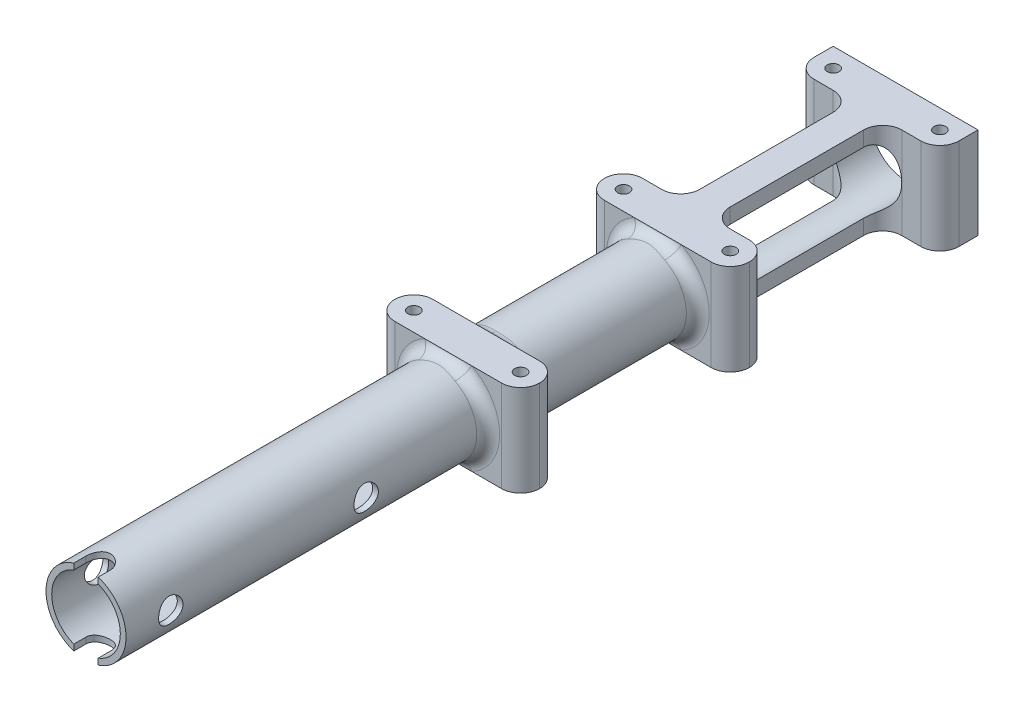
SolidWorks part; units mm, degrees
material "6063-T6"
ref_plane "Front Plane" through (0, 0, 0) normal (0, 0, 1) x (1, 0, 0)
ref_plane "Top Plane" through (0, 0, 0) normal (0, 1, 0) x (1, 0, 0)
ref_plane "Right Plane" through (0, 0, 0) normal (1, 0, 0) x (0, 0, -1)
sketch "Sketch1" plane through (0, 0, 0) normal (0, 0, 1) x (1, 0, 0)
  circle A1 centre (0, 0) radius 10.5
  dimension "D1" = 21
extrude "Boss-Extrude1" add sketch "Sketch1" along normal blind 150
sketch "Sketch3" plane through (0, 0, 0) normal (0, 1, 0) x (1, 0, 0)
  line L0 (0, 0) -> (0, 101.6874) construction
  line L2 (19, 0) -> (-19, 0)
  line L3 (-19, 0) -> (-19, 10)
  line L4 (-19, 10) -> (-4, 10)
  line L5 (-4, 10) -> (-4, 55)
  line L6 (-4, 55) -> (-19, 55)
  line L7 (-19, 55) -> (-19, 65)
  line L8 (-19, 65) -> (19, 65)
  line L9 (19, 55) -> (19, 65)
  line L10 (4, 55) -> (19, 55)
  line L11 (4, 10) -> (4, 55)
  line L12 (19, 10) -> (4, 10)
  line L13 (19, 0) -> (19, 10)
  line L14 (-19, 5) -> (35.7917, 5) construction
  line L15 (-19, 60) -> (20.8388, 60) construction
  line L16 (14, -50) -> (-14, -50) construction
  line L24 (0, -50) -> (0, 0) construction
  line L28 (-19, -55) -> (19, -55)
  line L29 (-19, -55) -> (-19, -45)
  line L30 (-19, -45) -> (19, -45)
  line L31 (19, -55) -> (19, -45)
  line L32 (-19, -55) -> (19, -45) construction
  line L33 (-19, -45) -> (19, -55) construction
  circle A0 centre (-14, 5) radius 1.55
  circle A1 centre (14, 5) radius 1.55
  circle A4 centre (-14, 60) radius 1.55
  circle A5 centre (14, 60) radius 1.55
  circle A6 centre (14, -50) radius 1.55
  circle A7 centre (-14, -50) radius 1.55
  point P12 (0, 65)
  dimension "D6" = 3.1
  dimension "D8" = 3.1
  dimension "D11" = 28
  dimension "D12" = 55
  dimension "D13" = 28
  dimension "D7" = 28
  dimension "D2" = 45
  dimension "D3" = 10
  dimension "D4" = 10
  dimension "D5" = 8
  dimension "D10" = 38
  dimension "D14" = 38
  dimension "D16" = 10
  dimension "D17" = 38
extrude "Boss-Extrude2" add sketch "Sketch3" along normal blind 12 and the other way blind 12
sketch "Sketch6" plane through (0, 0, 0) normal (0, 0, 1) x (1, 0, 0)
  circle A0 centre (0, 0) radius 9
  dimension "D1" = 18
extrude "Cut-Extrude1" cut sketch "Sketch6" against normal through all both and the other way through all
sketch "Sketch7" plane through (0, 0, 0) normal (1, 0, 0) x (0, 0, -1)
  line L0 (-150, 9) -> (-150, -9) construction
  line L1 (-138.25, 0) -> (0, 0) construction
  circle A0 centre (-87, 0) radius 3.2
  circle A1 centre (-138.25, 0) radius 3.2
  dimension "D1" = 6.4
  dimension "D2" = 11.75
  dimension "D3" = 63
extrude "Cut-Extrude2" cut sketch "Sketch7" against normal through all both and the other way through all
sketch "Sketch8" plane through (0, 0, 0) normal (0, 1, 0) x (1, 0, 0)
  line L0 (0, 0) -> (0, -186.8535) construction
  line L1 (3.2, -150) -> (-3.2, -150)
  line L2 (-3.2, -150) -> (-3.2, -146.8)
  line L3 (3.2, -150) -> (3.2, -146.8)
  line L4 (-10.5, -150) -> (10.5, -150) construction
  line L5 (-3.2, -146.8) -> (3.2, -146.8) construction
  arc A0 (-3.2, -146.8) -> (3.2, -146.8) centre (0, -146.8) cw
  point P9 (0, -150)
  dimension "D1" = 3.2
  dimension "D2" = 3.2
extrude "Cut-Extrude3" cut sketch "Sketch8" along normal up to next and the other way up to next
fillet "Fillet1" radius 5 18 edges at (-4, 10.0311, -55) (4, 10.0311, -55) (-4, 10.0311, -10) (4, 10.0311, -10) (-4, -10.0311, -55) (4, -10.0311, -55) (4, -10.0311, -10) (-4, -10.0311, -10) (-19, 0, -10) (-19, 0, 0) (-19, 0, -55) (19, 0, -55) (19, 0, -10) (19, 0, 0) (-19, 0, 45) (-19, 0, 55) (19, 0, 55) (19, 0, 45)
fillet "Fillet3" radius 3 3 edges at (10.5, 0, 0) (-10.5, 0, 45) (10.5, 0, 55)
